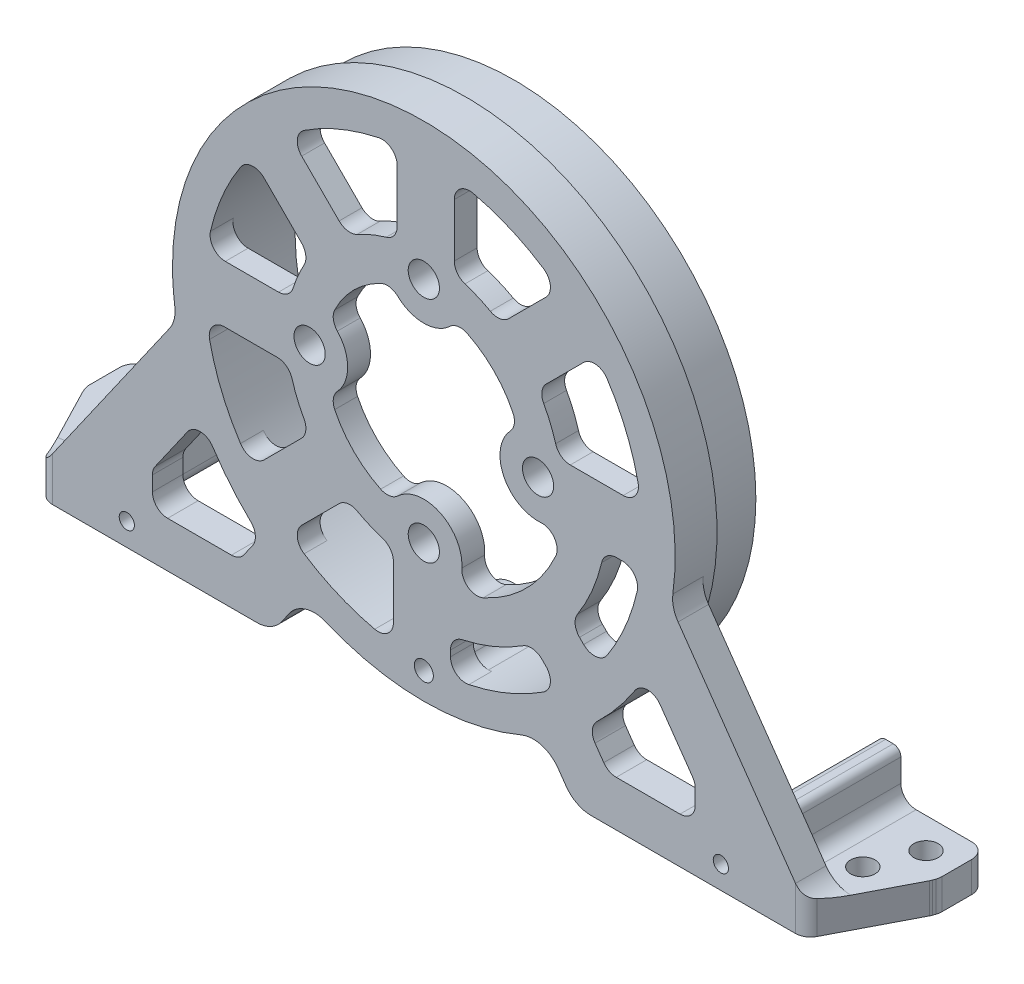
SolidWorks part; units mm, degrees
material "6061 合金"
ref_plane "前视基准面" through (0, 0, 0) normal (0, 0, 1) x (1, 0, 0)
ref_plane "上视基准面" through (0, 0, 0) normal (0, 1, 0) x (1, 0, 0)
ref_plane "右视基准面" through (0, 0, 0) normal (1, 0, 0) x (0, 0, -1)
sketch "草图1" plane through (0, 0, 0) normal (0, 0, 1) x (1, 0, 0)
  line L0 (0, 0) -> (0, 29.5) construction
  circle A0 centre (0, 0) radius 28.75
  circle A1 centre (0, 0) radius 31.75
  circle A2 centre (0, 0) radius 25 construction
  circle A3 centre (0, 0) radius 29.5 construction
  circle A4 centre (0, 29.5) radius 1.2 construction
  circle A5 centre (0, 29.5) radius 1.5 construction
  dimension "D1" = 63.5
  dimension "D2" = 50
  dimension "D3" = 59
  dimension "D4" = 3
  dimension "D5" = 2.4
  dimension "D6" = 3
  dimension "D7" = 2.25
extrude "凸台-拉伸1" add sketch "草图1" along normal blind 6.35
sketch "草图2" plane through (0, 0, 0) normal (1, 0, 0) x (0, 0, -1)
  line L0 (0, 0) -> (-35.4718, 0) construction
  line L1 (0, 0) -> (0, 47.506) construction
  line L2 (-6.35, 31.75) -> (-6.35, 33)
  line L3 (-6.35, 33) -> (-11.85, 33)
  line L4 (-11.85, 33) -> (-11.85, 28.75)
  line L5 (-11.85, 28.75) -> (-6.35, 28.75)
  line L6 (-6.35, 31.75) -> (-6.35, -31.75) construction
  line L7 (-6.35, 28.75) -> (-6.35, 31.75)
  line L8 (0, 28.75) -> (-6.35, 28.75) construction
  dimension "D1" = 5.5
  dimension "D2" = 66
revolve "旋转1" add sketch "草图2" angle 360 about L0
sketch "草图3" plane through (0, 0, 11.85) normal (0, 0, 1) x (1, 0, 0)
  line L0 (0, 0) -> (-50000, 0) construction
  line L1 (-3.5, 28.5362) -> (-3.5, 17.6564)
  line L2 (0, 0) -> (0, 50000) construction
  line L3 (-17.7032, 22.653) -> (-10.0101, 14.9599)
  line L4 (-28.4704, 4) -> (-17.5499, 4)
  line L5 (0, 0) -> (-20.3293, 20.3293) construction
  line L6 (-22.653, 17.7032) -> (-14.9599, 10.0101)
  line L7 (4, 28.4704) -> (4, 17.5499)
  line L8 (17.7032, 22.653) -> (10.0101, 14.9599)
  line L9 (22.653, 17.7032) -> (14.9599, 10.0101)
  line L10 (28.5362, 3.5) -> (17.6564, 3.5)
  line L11 (28.4704, -4) -> (23.6643, -4)
  line L12 (22.653, -17.7032) -> (19.264, -14.3143)
  line L13 (17.7032, -22.653) -> (14.3143, -19.264)
  line L14 (3.5, -28.5362) -> (3.5, -23.7434)
  line L15 (-4, -28.4704) -> (-4, -17.5499)
  line L16 (-17.7032, -22.653) -> (-10.0101, -14.9599)
  line L17 (-22.653, -17.7032) -> (-14.9599, -10.0101)
  line L18 (-28.5362, -3.5) -> (-17.6564, -3.5)
  arc A0 (12.3, 4.2083) -> (4.2083, 12.3) centre (0, 0) ccw
  circle A1 centre (0, 0) radius 28.75 construction
  arc A2 (-28.4704, 4) -> (-28.5362, -3.5) centre (0, 0) ccw
  circle A3 centre (0, 0) radius 15 construction
  circle A4 centre (15, 0) radius 2.05
  circle A6 centre (0, -15) radius 2.05
  arc A7 (3.363, -18.7) -> (-4.2083, -12.3) centre (0, -15) ccw
  circle A8 centre (-15, 0) radius 2.05
  circle A10 centre (0, 15) radius 2.05
  arc A12 (3.363, -18.7) -> (18.7, -3.363) centre (0, 0) ccw
  arc A13 (-12.3, -4.2083) -> (-4.2083, -12.3) centre (0, 0) ccw
  arc A14 (-12.3, -4.2083) -> (-12.3, 4.2083) centre (-15, 0) ccw
  arc A15 (3.5, -23.7434) -> (14.3143, -19.264) centre (0, 0) ccw
  arc A16 (12.3, 4.2083) -> (18.7, -3.363) centre (15, 0) ccw
  arc A17 (-4.2083, 12.3) -> (4.2083, 12.3) centre (0, 15) ccw
  arc A18 (-4.2083, 12.3) -> (-12.3, 4.2083) centre (0, 0) ccw
  arc A19 (-14.9599, 10.0101) -> (-17.5499, 4) centre (0, 0) ccw
  arc A20 (-17.7032, 22.653) -> (-22.653, 17.7032) centre (0, 0) ccw
  arc A21 (-17.6564, -3.5) -> (-14.9599, -10.0101) centre (0, 0) ccw
  arc A22 (-3.5, 17.6564) -> (-10.0101, 14.9599) centre (0, 0) ccw
  arc A23 (4, 28.4704) -> (-3.5, 28.5362) centre (0, 0) ccw
  arc A24 (10.0101, 14.9599) -> (4, 17.5499) centre (0, 0) ccw
  arc A25 (22.653, 17.7032) -> (17.7032, 22.653) centre (0, 0) ccw
  arc A26 (17.6564, 3.5) -> (14.9599, 10.0101) centre (0, 0) ccw
  arc A27 (28.4704, -4) -> (28.5362, 3.5) centre (0, 0) ccw
  arc A30 (-4, -28.4704) -> (3.5, -28.5362) centre (0, 0) ccw
  arc A31 (17.7032, -22.653) -> (22.653, -17.7032) centre (0, 0) ccw
  arc A32 (-22.653, -17.7032) -> (-17.7032, -22.653) centre (0, 0) ccw
  arc A33 (-10.0101, -14.9599) -> (-4, -17.5499) centre (0, 0) ccw
  arc A34 (19.264, -14.3143) -> (23.6643, -4) centre (0, 0) ccw
  point P25 (0, 0)
  point P66 (0, 0)
  dimension "D1" = 4.1
  dimension "D2" = 30
  dimension "D3" = 5
  dimension "D4" = 2
  dimension "D6" = 45
  dimension "D10" = 3
  dimension "D12" = 5
  dimension "D13" = 19
  dimension "D7" = 3.5
  dimension "D8" = 3.5
  dimension "D9" = 4
  dimension "D5" = 4
  dimension "D11" = 4
extrude "凸台-拉伸2" add sketch "草图3" against normal blind 3
fillet "圆角1" radius 2 40 edges at (12.3, 4.2083, 10.35) (18.7, -3.363, 10.35) (3.363, -18.7, 10.35) (-4.2083, -12.3, 10.35) (-12.3, -4.2083, 10.35) (-12.3, 4.2083, 10.35) (4.2083, 12.3, 10.35) (-4.2083, 12.3, 10.35) (-3.5, 17.6564, 10.35) (-10.0101, 14.9599, 10.35) (-17.7032, 22.653, 10.35) (-22.653, 17.7032, 10.35) (-14.9599, 10.0101, 10.35) (-17.5499, 4, 10.35) (-28.4704, 4, 10.35) (-28.5362, -3.5, 10.35) (-17.6564, -3.5, 10.35) (-14.9599, -10.0101, 10.35) (-22.653, -17.7032, 10.35) (-17.7032, -22.653, 10.35) (-10.0101, -14.9599, 10.35) (-4, -17.5499, 10.35) (-4, -28.4704, 10.35) (3.5, -28.5362, 10.35) (17.7032, -22.653, 10.35) (22.653, -17.7032, 10.35) (28.4704, -4, 10.35) (28.5362, 3.5, 10.35) (17.6564, 3.5, 10.35) (14.9599, 10.0101, 10.35) (22.653, 17.7032, 10.35) (17.7032, 22.653, 10.35) (10.0101, 14.9599, 10.35) (4, 17.5499, 10.35) (4, 28.4704, 10.35) (-3.5, 28.5362, 10.35) (14.3143, -19.264, 10.35) (23.6643, -4, 10.35) (3.5, -23.7434, 10.35) (19.264, -14.3143, 10.35)
sketch "草图4" plane through (0, 0, 11.85) normal (0, 0, 1) x (1, 0, 0)
  line L0 (0, 0) -> (-50000, 0) construction
  line L1 (0, 0) -> (0, 50000) construction
  line L2 (-1041.7591, -35) -> (-19.8795, -35) construction
  line L3 (-48.4278, -86.1637) -> (48.4278, -86.1637) construction
  line L4 (-44.4747, -79.6637) -> (44.4747, -79.6637) construction
  line L5 (50, -35) -> (19.8795, -35)
  line L6 (44.4747, -79.6637) -> (44.4747, -10.189) construction
  line L7 (50, -35) -> (50, -31)
  line L11 (-50, -35) -> (-50, -31)
  line L19 (50, -31) -> (32.4593, -5.9493)
  line L20 (-50, -31) -> (-32.4593, -5.9493)
  line L21 (25.8795, 67.4046) -> (-25.8795, 67.4046) construction
  line L22 (-25.8795, 67.4046) -> (-25.8795, -35) construction
  line L23 (-19.8795, -35) -> (-15.6975, -29.0274)
  line L24 (-19.8795, -35) -> (-50, -35)
  line L25 (19.8795, -35) -> (50000, -35) construction
  line L26 (19.8795, -35) -> (15.6975, -29.0274)
  circle A0 centre (0, -111.1637) radius 54.5 construction
  circle A1 centre (0, 0) radius 33 construction
  arc A2 (-32.4593, -5.9493) -> (-15.6975, -29.0274) centre (0, 0) ccw
  circle A3 centre (0, 97.9046) radius 40 construction
  arc A4 (15.6975, -29.0274) -> (32.4593, -5.9493) centre (0, 0) ccw
  point P28 (0, 67.4046)
  dimension "D2" = 109
  dimension "D9" = 80
  dimension "D1" = 35
  dimension "D3" = 25
  dimension "D4" = 31.5
  dimension "D5" = 35
  dimension "D6" = 4
  dimension "D7" = 100
  dimension "D8" = 5.5253
  dimension "D10" = 30.5
  dimension "D11" = 6
extrude "凸台-拉伸3" add sketch "草图4" against normal blind 4
sketch "草图5" plane through (0, -35, 0) normal (0, -1, 0) x (1, 0, 0)
  line L0 (0, 0) -> (0, -50000) construction
  line L1 (-28.75, 0) -> (28.75, 0) construction
  line L2 (-33, 6.35) -> (33, 6.35) construction
  line L3 (-49.6387, -41.763) -> (49.6387, -41.763) construction
  line L4 (-53.8164, -55.6582) -> (53.8164, -55.6582) construction
  line L5 (0, -64.263) -> (54.5, -64.263) construction
  line L6 (51.9423, -47.763) -> (0, -47.763) construction
  line L7 (49.6387, -41.763) -> (49.6387, 12.4747) construction
  line L8 (0, 3.85) -> (49.6387, 3.85) construction
  line L10 (51.9423, -47.763) -> (51.9423, -2.15) construction
  line L11 (51.9423, -2.15) -> (0, -2.15) construction
  line L12 (55.9423, -6.15) -> (41.6387, -6.15)
  line L13 (41.6387, -6.15) -> (41.6387, 7.85)
  line L14 (50, 11.85) -> (55.6577, 0.9261)
  line L15 (55.9423, 0.0973) -> (55.9423, -6.15)
  line L16 (50, 11.85) -> (50, 7.85)
  line L17 (50, 7.85) -> (41.6387, 7.85)
  line L18 (-50, 11.85) -> (-50, 7.85)
  line L19 (-50, 11.85) -> (-55.6577, 0.9261)
  line L20 (-55.9423, 0.0973) -> (-55.9423, -6.15)
  line L21 (-55.9423, -6.15) -> (-41.6387, -6.15)
  line L22 (-41.6387, -6.15) -> (-41.6387, 7.85)
  line L23 (-50, 7.85) -> (-41.6387, 7.85)
  line L24 (29.4713, -47.763) -> (29.4713, -41.763) construction
  line L26 (33.6692, -2.15) -> (33.6692, 3.85) construction
  line L27 (19.8795, 11.85) -> (50, 11.85) construction
  line L28 (19.8795, 7.85) -> (50, 7.85) construction
  circle A0 centre (0, -64.263) radius 54.5 construction
  circle A1 centre (49.6387, 3.85) radius 3 construction
  circle A2 centre (51.9423, -2.15) radius 3 construction
  circle A3 centre (49.6387, 3.85) radius 1.6
  circle A4 centre (51.9423, -2.15) radius 1.6
  circle A5 centre (-49.6387, 3.85) radius 1.6
  circle A6 centre (-51.9423, -2.15) radius 1.6
  arc A7 (55.9423, 0.0973) -> (55.6577, 0.9261) centre (0, -18.65) ccw
  arc A8 (-55.9423, 0.0973) -> (-55.6577, 0.9261) centre (0, -18.65) cw
  point P4 (0, 0)
  point P13 (0, -41.763)
  point P15 (0, -55.6582)
  dimension "D1" = 109
  dimension "D5" = 6
  dimension "D7" = 4
  dimension "D6" = 3.2
  dimension "D11" = 59
  dimension "D2" = 22.5
  dimension "D3" = 6
  dimension "D4" = 8
  dimension "D8" = 4
  dimension "D9" = 8
  dimension "D10" = 4
  dimension "D12" = 25
extrude "凸台-拉伸4" add sketch "草图5" against normal blind 4
sketch "草图7" plane through (0, 0, 7.85) normal (0, 0, -1) x (-1, 0, 0)
  line L0 (-41.6387, -31) -> (-55.9423, -31) construction
  line L1 (-44.6387, -31) -> (-41.6387, -31)
  line L2 (-44.6387, -31) -> (-44.6387, -25)
  line L4 (-41.6387, -31) -> (-41.6387, -25)
  line L6 (-41.6387, -31) -> (-41.6387, -35) construction
  line L8 (0, 0) -> (0, -39.7814) construction
  line L10 (41.6387, -31) -> (41.6387, -25)
  line L11 (44.6387, -31) -> (44.6387, -25)
  line L12 (44.6387, -31) -> (41.6387, -31)
  line L13 (-41.6387, -25) -> (-44.6387, -25)
  line L14 (-50, -31) -> (-41.6387, -31) construction
  line L15 (41.6387, -25) -> (44.6387, -25)
  circle A0 centre (0, 0) radius 47 construction
  dimension "D2" = 94
  dimension "D1" = 3
  dimension "D3" = 6
extrude "凸台-拉伸5" add sketch "草图7" along normal up to surface (14 mm away) up to face at (48.7905, -33, -6.15)
fillet "圆角2" radius 4 8 edges at (50, -31, 9.85) (-50, -31, 9.85) (32.4593, -5.9493, 9.85) (-32.4593, -5.9493, 9.85) (19.8795, -35, 9.85) (15.6975, -29.0274, 9.85) (-19.8795, -35, 9.85) (-15.6975, -29.0274, 9.85)
fillet "圆角3" radius 2 12 edges at (44.6387, -31, 0.85) (-44.6387, -31, 0.85) (41.6387, -35, 0.85) (-50, -32.7076, 11.85) (50, -32.7076, 11.85) (55.9423, -33, -6.15) (-55.9423, -33, -6.15) (-41.6387, -35, 0.85) (55.6577, -33, 0.9261) (55.9423, -33, 0.0973) (-55.9423, -33, 0.0973) (-55.6577, -33, 0.9261)
fillet "圆角4" radius 1 4 edges at (41.6387, -25, 0.85) (44.6387, -25, 0.85) (-41.6387, -25, 0.85) (-44.6387, -25, 0.85)
sketch "草图9" plane through (0, 0, 7.85) normal (0, 0, -1) x (-1, 0, 0)
  line L1 (-21.9618, -35) -> (-43.6387, -35) construction
  line L2 (0, 0) -> (0, -43.2914) construction
  circle A0 centre (0, 0) radius 47.5 construction
  circle A1 centre (-39, -32) radius 1
  circle A2 centre (-39, -32) radius 1.75 construction
  circle A3 centre (-39, -32) radius 2.5 construction
  circle A4 centre (39, -32) radius 1
  dimension "D1" = 95
  dimension "D2" = 2
  dimension "D3" = 3.5
  dimension "D4" = 5
  dimension "D5" = 78
  dimension "D6" = 3
extrude "切除-拉伸1" cut sketch "草图9" against normal through all
sketch "草图12" plane through (0, 0, 7.85) normal (0, 0, -1) x (-1, 0, 0)
  line L0 (24.2237, -29) -> (35.6387, -29)
  line L1 (35.6387, -29) -> (35.6387, -24.4375)
  line L2 (35.6387, -24.4375) -> (29.2396, -15.2986)
  line L3 (24.2237, -29) -> (21.4671, -25.0632)
  line L4 (43.6387, -35) -> (21.9618, -35) construction
  line L5 (41.6387, -26) -> (41.6387, -33) construction
  line L6 (33.3868, -7.2739) -> (48.8057, -29.2943) construction
  line L8 (18.6852, -33.2943) -> (17.6413, -31.8034) construction
  line L9 (0, 0) -> (0, -41.4945) construction
  line L10 (-24.2237, -29) -> (-35.6387, -29)
  line L11 (-35.6387, -29) -> (-35.6387, -24.4375)
  line L12 (-35.6387, -24.4375) -> (-29.2396, -15.2986)
  line L13 (-24.2237, -29) -> (-21.4671, -25.0632)
  arc A0 (12.8117, -30.4115) -> (32.6998, -4.4412) centre (0, 0) ccw construction
  arc A1 (21.4671, -25.0632) -> (29.2396, -15.2986) centre (0, 0) ccw
  arc A2 (-21.4671, -25.0632) -> (-29.2396, -15.2986) centre (0, 0) cw
  dimension "D1" = 6
  dimension "D2" = 6
  dimension "D3" = 8
  dimension "D4" = 7
extrude "切除-拉伸3" cut sketch "草图12" against normal blind 10
fillet "圆角6" radius 2 10 edges at (-29.2396, -15.2986, 9.85) (-35.6387, -24.4375, 9.85) (-35.6387, -29, 9.85) (-24.2237, -29, 9.85) (-21.4671, -25.0632, 9.85) (21.4671, -25.0632, 9.85) (24.2237, -29, 9.85) (35.6387, -29, 9.85) (35.6387, -24.4375, 9.85) (29.2396, -15.2986, 9.85)
sketch "草图10" plane through (0, 0, 11.85) normal (0, 0, 1) x (1, 0, 0)
  line L0 (0, 0) -> (0, -29.5) construction
  circle A0 centre (0, 0) radius 29.5 construction
  circle A1 centre (0, -29.5) radius 1
  dimension "D1" = 59
  dimension "D2" = 2
extrude "切除-拉伸2" cut sketch "草图10" against normal blind 2
sketch "草图11" plane through (0, 0, 8.85) normal (0, 0, -1) x (-1, 0, 0)
  arc A0 (3.87, -28.4883) -> (-3.87, -28.4883) centre (0, -29.5) ccw
  arc A1 (-5.9112, -28.1357) -> (6.4486, -28.0175) centre (0, 0) ccw construction
  arc A2 (-3.87, -28.4883) -> (3.87, -28.4883) centre (0, 0) ccw
  dimension "D1" = 8
  dimension "D2" = 29.5
extrude "凸台-拉伸6" add sketch "草图11" along normal up to surface (8.85 mm away) up to face at (31.75, 0, 0)
fillet "圆角5" radius 2 2 edges at (3.87, -28.4883, 4.425) (-3.87, -28.4883, 4.425)
hole_wizard "M3 螺纹孔1" positions "3D草图1" profile "草图13" tap size "M3" standard "GB"
sketch3d "3D草图1"
  line L0 (0, -29.5, 9.85) -> (0, -29.5, 11.85) construction
  point P0 (0, -29.5, 11.85)
sketch "草图13" plane through (0, -29.5, 11.85) normal (1, 0, 0) x (0, -1, 0)
  line L0 (0, 0) -> (0, 8.2511)
  line L1 (0, 8.2511) -> (1.25, 7.5)
  line L2 (1.25, 7.5) -> (1.25, 0)
  line L5 (1.25, 0) -> (0, 0)
  line L10 (0, 8.2511) -> (-1.25, 7.5) construction
  line L11 (0, -6.35) -> (0, 107.95) construction
  dimension "螺纹孔钻头直径" = 2.5
  dimension "螺纹孔钻头深度" = 7.5
  dimension "导头角度" = 118
cosmetic thread "孔螺蚊线1" parameters "D1"=5, "D2"=3
sketch "草图14" plane through (0, 0, 8.85) normal (0, 0, -1) x (-1, 0, 0)
  circle A0 centre (0, 0) radius 23.5
  dimension "D1" = 47
